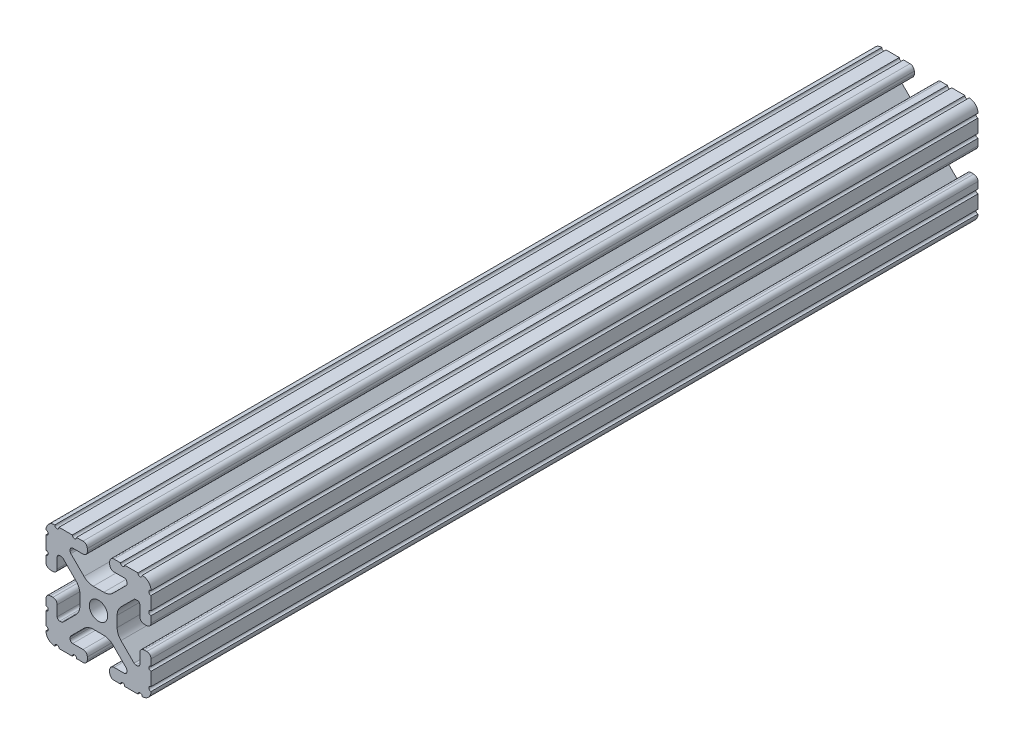
SolidWorks part; units mm, degrees
material "6061 Alloy"
ref_plane "Front Plane" through (0, 0, 0) normal (0, 0, 1) x (1, 0, 0)
ref_plane "Top Plane" through (0, 0, 0) normal (0, 1, 0) x (1, 0, 0)
ref_plane "Right Plane" through (0, 0, 0) normal (1, 0, 0) x (0, 0, -1)
sketch "Sketch1" plane through (0, 0, 0) normal (0, 0, 1) x (1, 0, 0)
  line L0 (0, 25.6181) -> (0, -24.623) construction
  line L1 (-20.8943, 0) -> (20.4607, 0) construction
  line L2 (-10.0229, 12.9148) -> (-5.2522, 8.144)
  line L3 (-10.287, 14.0843) -> (-10.287, 13.5524)
  line L4 (-5.6176, 14.986) -> (-9.3853, 14.986)
  line L5 (-4.064, 17.4964) -> (-4.064, 16.5396)
  line L6 (-7.9742, 19.05) -> (-5.6176, 19.05)
  line L7 (-14.3277, 19.05) -> (-9.4982, 19.05)
  line L8 (-19.05, 9.4961) -> (-19.05, 14.3277)
  line L9 (-19.05, 5.6176) -> (-19.05, 7.9763)
  line L10 (-16.5396, 4.064) -> (-17.4964, 4.064)
  line L11 (-14.986, 9.3853) -> (-14.986, 5.6176)
  line L12 (-13.516, 10.287) -> (-14.0843, 10.287)
  line L13 (-8.1476, 5.2921) -> (-12.8784, 10.0229)
  line L14 (-6.7564, -1.9335) -> (-6.7564, 1.9335)
  line L15 (-12.8784, -10.0229) -> (-8.1476, -5.2921)
  line L16 (-14.0843, -10.287) -> (-13.516, -10.287)
  line L17 (-14.986, -5.6176) -> (-14.986, -9.3853)
  line L18 (-17.4964, -4.064) -> (-16.5396, -4.064)
  line L19 (-19.05, -7.9763) -> (-19.05, -5.6176)
  line L20 (-19.05, -14.3277) -> (-19.05, -9.4961)
  line L21 (-9.4961, -19.05) -> (-14.3277, -19.05)
  line L22 (-5.6176, -19.05) -> (-7.9763, -19.05)
  line L23 (-4.064, -17.4964) -> (-4.064, -16.5396)
  line L24 (10.0229, -12.9148) -> (5.2522, -8.144)
  line L25 (10.287, -14.0843) -> (10.287, -13.5524)
  line L26 (5.6176, -14.986) -> (9.3853, -14.986)
  line L28 (-1.9022, 6.7564) -> (1.9022, 6.7564)
  line L29 (-1.9022, -6.7564) -> (1.9022, -6.7564)
  line L31 (-5.6176, -14.986) -> (-9.3853, -14.986)
  line L32 (-10.287, -14.0843) -> (-10.287, -13.5524)
  line L33 (-10.0229, -12.9148) -> (-5.2522, -8.144)
  line L66 (4.064, -16.5396) -> (4.064, -17.4964)
  line L67 (5.6176, -19.05) -> (7.9763, -19.05)
  line L68 (9.4961, -19.05) -> (14.3277, -19.05)
  line L69 (19.05, -14.3277) -> (19.05, -9.4961)
  line L70 (19.05, -7.9763) -> (19.05, -5.6176)
  line L71 (17.4964, -4.064) -> (16.5396, -4.064)
  line L72 (14.986, -5.6176) -> (14.986, -9.3853)
  line L73 (14.0843, -10.287) -> (13.516, -10.287)
  line L74 (12.8784, -10.0229) -> (8.1476, -5.2921)
  line L75 (6.7564, -1.9335) -> (6.7564, 1.9335)
  line L76 (8.1476, 5.2921) -> (12.8784, 10.0229)
  line L77 (13.516, 10.287) -> (14.0843, 10.287)
  line L78 (14.986, 9.3853) -> (14.986, 5.6176)
  line L79 (16.5396, 4.064) -> (17.4964, 4.064)
  line L80 (19.05, 5.6176) -> (19.05, 7.9763)
  line L81 (19.05, 9.4961) -> (19.05, 14.3277)
  line L82 (14.3277, 19.05) -> (9.4982, 19.05)
  line L83 (7.9742, 19.05) -> (5.6176, 19.05)
  line L84 (4.064, 17.4964) -> (4.064, 16.5396)
  line L85 (5.6176, 14.986) -> (9.3853, 14.986)
  line L86 (10.287, 14.0843) -> (10.287, 13.5524)
  line L87 (10.0229, 12.9148) -> (5.2522, 8.144)
  arc A0 (-10.0229, 12.9148) -> (-10.287, 13.5524) centre (-9.3853, 13.5524) cw
  circle A1 centre (0, 0) radius 3.3274
  arc A2 (-10.287, 14.0843) -> (-9.3853, 14.986) centre (-9.3853, 14.0843) cw
  arc A3 (-4.064, 16.5396) -> (-5.6176, 14.986) centre (-5.6176, 16.5396) cw
  arc A4 (-5.6176, 19.05) -> (-4.064, 17.4964) centre (-5.6176, 17.4964) cw
  arc A5 (-7.9742, 19.05) -> (-9.4982, 19.05) centre (-8.7362, 19.05) cw
  arc A6 (-14.3277, 19.05) -> (-15.8475, 19.05) centre (-15.0876, 18.9933) cw
  arc A7 (-19.05, 15.8475) -> (-15.8475, 19.05) centre (-15.8751, 15.8751) cw
  arc A8 (-19.05, 15.8475) -> (-19.05, 14.3277) centre (-18.9933, 15.0876) cw
  arc A9 (-19.05, 9.4961) -> (-19.05, 7.9763) centre (-18.9933, 8.7362) cw
  arc A10 (-17.4964, 4.064) -> (-19.05, 5.6176) centre (-17.4964, 5.6176) cw
  arc A11 (-14.986, 5.6176) -> (-16.5396, 4.064) centre (-16.5396, 5.6176) cw
  arc A12 (-14.986, 9.3853) -> (-14.0843, 10.287) centre (-14.0843, 9.3853) cw
  arc A13 (-13.516, 10.287) -> (-12.8784, 10.0229) centre (-13.516, 9.3853) cw
  arc A14 (-8.1476, 5.2921) -> (-6.7564, 1.9335) centre (-11.5062, 1.9335) cw
  arc A15 (-6.7564, -1.9335) -> (-8.1476, -5.2921) centre (-11.5062, -1.9335) cw
  arc A16 (-12.8784, -10.0229) -> (-13.516, -10.287) centre (-13.516, -9.3853) cw
  arc A17 (-14.0843, -10.287) -> (-14.986, -9.3853) centre (-14.0843, -9.3853) cw
  arc A18 (-16.5396, -4.064) -> (-14.986, -5.6176) centre (-16.5396, -5.6176) cw
  arc A19 (-19.05, -5.6176) -> (-17.4964, -4.064) centre (-17.4964, -5.6176) cw
  arc A20 (-19.05, -7.9763) -> (-19.05, -9.4961) centre (-18.9933, -8.7362) cw
  arc A21 (-19.05, -14.3277) -> (-19.05, -15.8475) centre (-18.9933, -15.0876) cw
  arc A22 (-15.8475, -19.05) -> (-19.05, -15.8475) centre (-15.8751, -15.8751) cw
  arc A23 (-15.8475, -19.05) -> (-14.3277, -19.05) centre (-15.0876, -18.9933) cw
  arc A24 (-9.4961, -19.05) -> (-7.9763, -19.05) centre (-8.7362, -18.9933) cw
  arc A25 (-4.064, -17.4964) -> (-5.6176, -19.05) centre (-5.6176, -17.4964) cw
  arc A26 (-5.2522, -8.144) -> (-1.9022, -6.7564) centre (-1.9022, -11.494) cw
  arc A27 (1.9022, -6.7564) -> (5.2522, -8.144) centre (1.9022, -11.494) cw
  arc A28 (10.0229, -12.9148) -> (10.287, -13.5524) centre (9.3853, -13.5524) cw
  arc A29 (10.287, -14.0843) -> (9.3853, -14.986) centre (9.3853, -14.0843) cw
  arc A30 (4.064, -16.5396) -> (5.6176, -14.986) centre (5.6176, -16.5396) cw
  arc A31 (-4.064, -16.5396) -> (-5.6176, -14.986) centre (-5.6176, -16.5396) ccw
  arc A32 (-10.287, -14.0843) -> (-9.3853, -14.986) centre (-9.3853, -14.0843) ccw
  arc A33 (-10.0229, -12.9148) -> (-10.287, -13.5524) centre (-9.3853, -13.5524) ccw
  arc A79 (4.064, -17.4964) -> (5.6176, -19.05) centre (5.6176, -17.4964) ccw
  arc A80 (9.4961, -19.05) -> (7.9763, -19.05) centre (8.7362, -18.9933) ccw
  arc A81 (15.8475, -19.05) -> (14.3277, -19.05) centre (15.0876, -18.9933) ccw
  arc A82 (15.8475, -19.05) -> (19.05, -15.8475) centre (15.8751, -15.8751) ccw
  arc A83 (19.05, -14.3277) -> (19.05, -15.8475) centre (18.9933, -15.0876) ccw
  arc A84 (19.05, -7.9763) -> (19.05, -9.4961) centre (18.9933, -8.7362) ccw
  arc A85 (19.05, -5.6176) -> (17.4964, -4.064) centre (17.4964, -5.6176) ccw
  arc A86 (16.5396, -4.064) -> (14.986, -5.6176) centre (16.5396, -5.6176) ccw
  arc A87 (14.0843, -10.287) -> (14.986, -9.3853) centre (14.0843, -9.3853) ccw
  arc A88 (12.8784, -10.0229) -> (13.516, -10.287) centre (13.516, -9.3853) ccw
  arc A89 (6.7564, -1.9335) -> (8.1476, -5.2921) centre (11.5062, -1.9335) ccw
  arc A90 (8.1476, 5.2921) -> (6.7564, 1.9335) centre (11.5062, 1.9335) ccw
  arc A91 (13.516, 10.287) -> (12.8784, 10.0229) centre (13.516, 9.3853) ccw
  arc A92 (14.986, 9.3853) -> (14.0843, 10.287) centre (14.0843, 9.3853) ccw
  arc A93 (14.986, 5.6176) -> (16.5396, 4.064) centre (16.5396, 5.6176) ccw
  arc A94 (17.4964, 4.064) -> (19.05, 5.6176) centre (17.4964, 5.6176) ccw
  arc A95 (19.05, 9.4961) -> (19.05, 7.9763) centre (18.9933, 8.7362) ccw
  arc A96 (19.05, 15.8475) -> (19.05, 14.3277) centre (18.9933, 15.0876) ccw
  arc A97 (19.05, 15.8475) -> (15.8475, 19.05) centre (15.8751, 15.8751) ccw
  arc A98 (14.3277, 19.05) -> (15.8475, 19.05) centre (15.0876, 18.9933) ccw
  arc A99 (7.9742, 19.05) -> (9.4982, 19.05) centre (8.7362, 19.05) ccw
  arc A100 (5.6176, 19.05) -> (4.064, 17.4964) centre (5.6176, 17.4964) ccw
  arc A101 (4.064, 16.5396) -> (5.6176, 14.986) centre (5.6176, 16.5396) ccw
  arc A102 (10.287, 14.0843) -> (9.3853, 14.986) centre (9.3853, 14.0843) ccw
  arc A103 (10.0229, 12.9148) -> (10.287, 13.5524) centre (9.3853, 13.5524) ccw
  arc A104 (1.9022, 6.7564) -> (5.2522, 8.144) centre (1.9022, 11.494) ccw
  arc A105 (-5.2522, 8.144) -> (-1.9022, 6.7564) centre (-1.9022, 11.494) ccw
  dimension "D1" = 6.6548
  dimension "D2" = 19.05
  dimension "D3" = 38.1
  dimension "D4" = 20.574
  dimension "D5" = 13.5128
  dimension "D6" = 4.064
  dimension "D7" = 8.128
  dimension "D8" = 4.064
  dimension "D9" = 12.2936
extrude "Extrude1" add sketch "Sketch1" against normal blind 300
